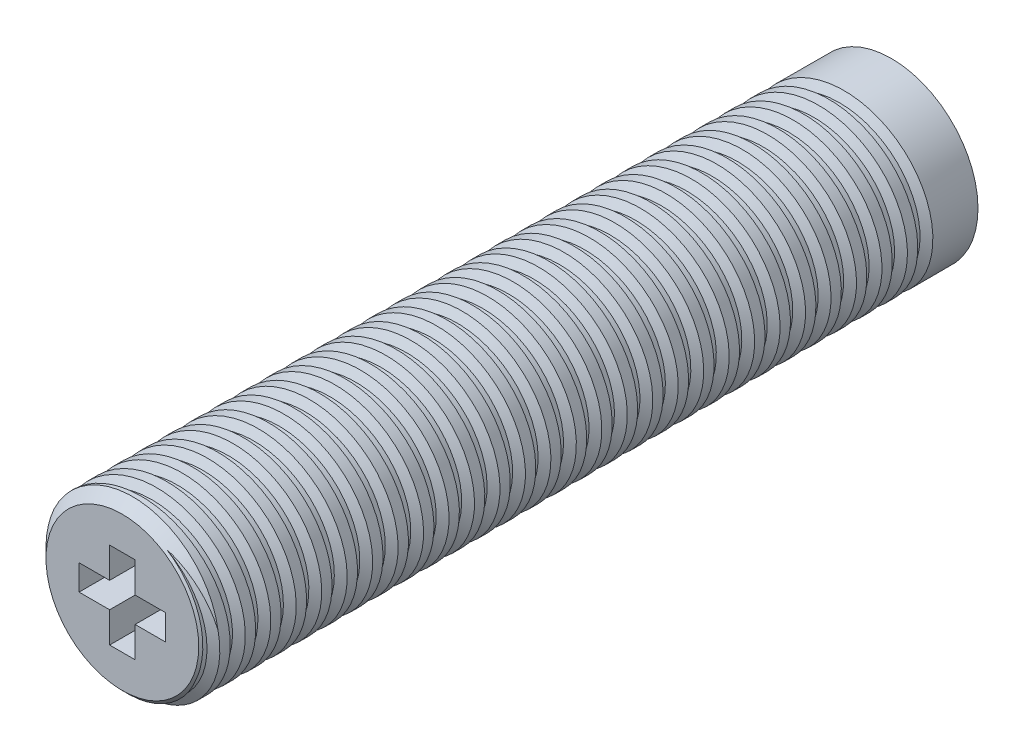
SolidWorks part; units mm, degrees
ref_plane "Front Plane" through (0, 0, 0) normal (0, 0, 1) x (1, 0, 0)
ref_plane "Top Plane" through (0, 0, 0) normal (0, 1, 0) x (1, 0, 0)
ref_plane "Right Plane" through (0, 0, 0) normal (1, 0, 0) x (0, 0, -1)
sketch "Sketch1" plane through (0, 0, 0) normal (0, 0, 1) x (1, 0, 0)
  circle A0 centre (0, 0) radius 8.5
  dimension "D1" = 17
extrude "Boss-Extrude1" add sketch "Sketch1" along normal blind 75.5
chamfer "Chamfer1" distance 1 angle 45 1 edges at (8.5, 0, 75.5)
ref_plane "Plane1" through (0, 0, 75.5) normal (0, 0, 1) x (1, 0, 0)
sketch "Sketch3" plane through (0, 0, 75.5) normal (0, 0, 1) x (1, 0, 0)
  circle A0 centre (0, 0) radius 8.5
  dimension "D1" = 17
sketch "Sketch4" plane through (0, 0, 0) normal (0, 1, 0) x (1, 0, 0)
  line L0 (-8.6, -75.6307) -> (-8.6, -77.2307)
  line L1 (-8.6, -77.2307) -> (-7.7, -76.7111)
  line L2 (-7.7, -76.7111) -> (-7.7, -76.1503)
  line L3 (-7.7, -76.1503) -> (-8.6, -75.6307)
  line L4 (-8.5, -74.5) -> (-8.5, -86.7444) construction
  dimension "D1" = 1.6
  dimension "D2" = 0.9
  dimension "D3" = 60
curve "Helix/Spiral1" pitch 2.5 height 72.5 radius 8.5 centre (0, 0, 75.5) axis (0, 0, -1) start towards (1, 0, 0)
sweep "Cut-Sweep2" cut profiles "Sketch4" path "Helix/Spiral1"
sketch "Sketch6" plane through (0, 0, 0) normal (0, 0, 1) x (1, 0, 0)
  line L1 (4, 2) -> (-4, 2)
  line L2 (4, 2) -> (4, -2)
  line L3 (4, -2) -> (-4, -2)
  line L4 (-4, 2) -> (-4, -2)
  point P4 (0, 2)
  point P5 (-4, 0)
  dimension "D1" = 8
  dimension "D2" = 4
extrude "Cut-Extrude1" cut sketch "Sketch6" along normal blind 8
sketch "Sketch7" plane through (0, 0, 0) normal (0, 0, 1) x (1, 0, 0)
  text T0 "<b>CW</b>" font "Century Gothic" height 2.5
extrude "Cut-Extrude2" cut sketch "Sketch7" along normal blind 1.5
sketch "Sketch8" plane through (0, 0, 75.5) normal (0, 0, 1) x (1, 0, 0)
  line L1 (-1.25, 4.25) -> (1.25, 4.25)
  line L2 (-1.25, 4.25) -> (-1.25, -4.25)
  line L3 (-1.25, -4.25) -> (1.25, -4.25)
  line L4 (1.25, 4.25) -> (1.25, -4.25)
  line L5 (-4.25, 1.25) -> (4.25, 1.25)
  line L6 (-4.25, 1.25) -> (-4.25, -1.25)
  line L7 (-4.25, -1.25) -> (4.25, -1.25)
  line L8 (4.25, 1.25) -> (4.25, -1.25)
  point P8 (0, 4.25)
  point P9 (1.25, 0)
  point P10 (0, 1.25)
  point P11 (4.25, 0)
  point P12 (0, 0)
  dimension "D1" = 2.5
  dimension "D2" = 2.5
  dimension "D3" = 8.5
  dimension "D4" = 8.5
extrude "Cut-Extrude3" cut sketch "Sketch8" against normal blind 11 contours L2 L5 L4 L1 | L2 L7 L4 L5 | L6 L7 L2 L5 | L8 L5 L4 L7 | L7 L2 L3 L4 region at (0, 2.75, 75.5) region at (0, 0, 75.5) region at (-2.75, 0, 75.5) region at (2.75, 0, 75.5) region at (0, -2.75, 75.5)
